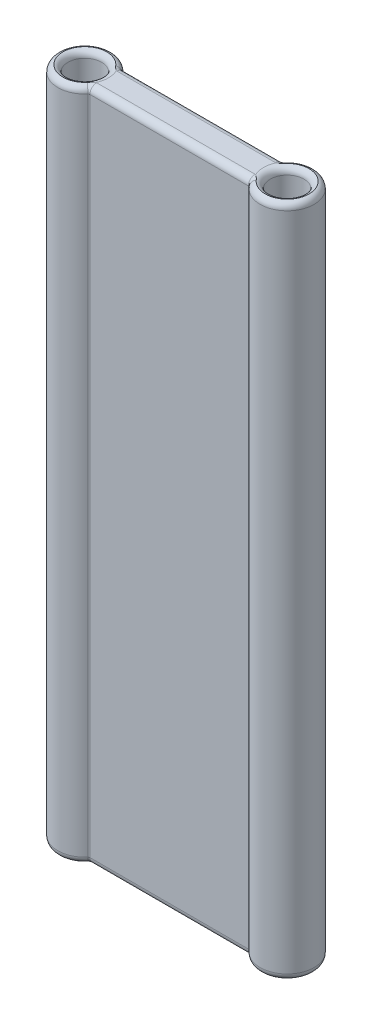
SolidWorks part; units mm, degrees
material "Custom Plastic"
ref_plane "Front Plane" through (0, 0, 0) normal (0, 0, 1) x (1, 0, 0)
ref_plane "Top Plane" through (0, 0, 0) normal (0, 1, 0) x (1, 0, 0)
ref_plane "Right Plane" through (0, 0, 0) normal (1, 0, 0) x (0, 0, -1)
sketch "Sketch1" plane through (0, 0, 0) normal (0, 1, 0) x (1, 0, 0)
  line L0 (-42.5677, 0) -> (42.5677, 0) construction
  line L3 (0, 39.8475) -> (0, -21.5223) construction
  line L8 (29.845, -6.35) -> (-29.845, -6.35)
  line L9 (-29.845, 6.35) -> (29.845, 6.35)
  circle A2 centre (38.1, 0) radius 6.35
  circle A3 centre (-38.1, 0) radius 6.35
  arc A4 (-48.26, 0) -> (-30.3685, 6.5916) centre (-38.1, 0) cw
  arc A5 (30.3685, -6.5916) -> (48.26, 0) centre (38.1, 0) ccw
  circle A6 centre (-38.1, 0) radius 10.16 construction
  arc A7 (-30.3685, -6.5916) -> (-48.26, 0) centre (-38.1, 0) cw
  circle A8 centre (38.1, 0) radius 10.16 construction
  arc A9 (48.26, 0) -> (30.3685, 6.5916) centre (38.1, 0) ccw
  arc A12 (29.845, 6.35) -> (30.3685, 6.5916) centre (29.845, 7.0379) ccw
  arc A13 (29.845, -6.35) -> (30.3685, -6.5916) centre (29.845, -7.0379) cw
  arc A14 (-29.845, -6.35) -> (-30.3685, -6.5916) centre (-29.845, -7.0379) ccw
  arc A15 (-29.845, 6.35) -> (-30.3685, 6.5916) centre (-29.845, 7.0379) cw
  point P3 (0, 0)
  point P32 (46.0311, 6.35)
  point P39 (-30.1689, -6.35)
  point P46 (-46.0311, -6.35)
  dimension "D1" = 96.52
  dimension "D2" = 12.7
  dimension "D7" = 59.69
  dimension "D3" = 38.1
  dimension "D4" = 3.81
  dimension "D6" = 12.7
  dimension "D5" = 3.81
extrude "Boss-Extrude1" add sketch "Sketch1" along normal mid plane 254
fillet "Fillet1" radius 2.54 20 edges at (38.1, -127, 6.35) (-38.1, -127, -6.35) (-48.26, -127, 0) (-30.1333, -127, 6.4133) (0, -127, 6.35) (30.1333, -127, 6.4133) (48.26, -127, 0) (30.1333, -127, -6.4133) (0, -127, -6.35) (-30.1333, -127, -6.4133) (38.1, 127, 6.35) (-48.26, 127, 0) (-30.1333, 127, -6.4133) (0, 127, -6.35) (30.1333, 127, -6.4133) (48.26, 127, 0) (30.1333, 127, 6.4133) (0, 127, 6.35) (-30.1333, 127, 6.4133) (-38.1, 127, -6.35)
sketch "Sketch3" plane through (0, 0, -6.35) normal (0, 0, -1) x (-1, 0, 0)
  line L0 (26.9875, -2.2101) -> (26.9875, -96.1901) construction
  line L1 (26.9875, -2.2101) -> (-26.9875, -2.2101) construction
  line L2 (-26.9875, -2.2101) -> (-26.9875, -96.1901) construction
  line L3 (26.9875, -96.1901) -> (-26.9875, -96.1901) construction
  line L4 (26.9875, -2.2101) -> (-26.9875, -96.1901) construction
  line L5 (-26.9875, -2.2101) -> (26.9875, -96.1901) construction
  line L6 (24.765, 3.6639) -> (24.765, 102.9779) construction
  line L7 (24.765, 3.6639) -> (-24.765, 3.6639) construction
  line L8 (-24.765, 3.6639) -> (-24.765, 102.9779) construction
  line L9 (24.765, 102.9779) -> (-24.765, 102.9779) construction
  line L10 (24.765, 3.6639) -> (-24.765, 102.9779) construction
  line L11 (-24.765, 3.6639) -> (24.765, 102.9779) construction
  circle A0 centre (-26.9875, -96.1901) radius 0.9525
  circle A1 centre (-26.9875, -2.2101) radius 0.9525
  circle A2 centre (26.9875, -2.2101) radius 0.9525
  circle A3 centre (26.9875, -96.1901) radius 0.9525
  circle A4 centre (-24.765, 3.6639) radius 0.9525
  circle A5 centre (-24.765, 102.9779) radius 0.9525
  circle A6 centre (24.765, 102.9779) radius 0.9525
  circle A7 centre (24.765, 3.6639) radius 0.9525
  point P0 (0, -49.2001)
  point P9 (0, 0)
  point P10 (0, 53.3209)
  point P20 (0, 0)
  dimension "D3" = 1.905
  dimension "D6" = 1.905
  dimension "D1" = 53.975
  dimension "D2" = 93.98
  dimension "D4" = 49.53
  dimension "D5" = 99.314
extrude "Cut-Extrude1" cut sketch "Sketch3" against normal blind 3.81
